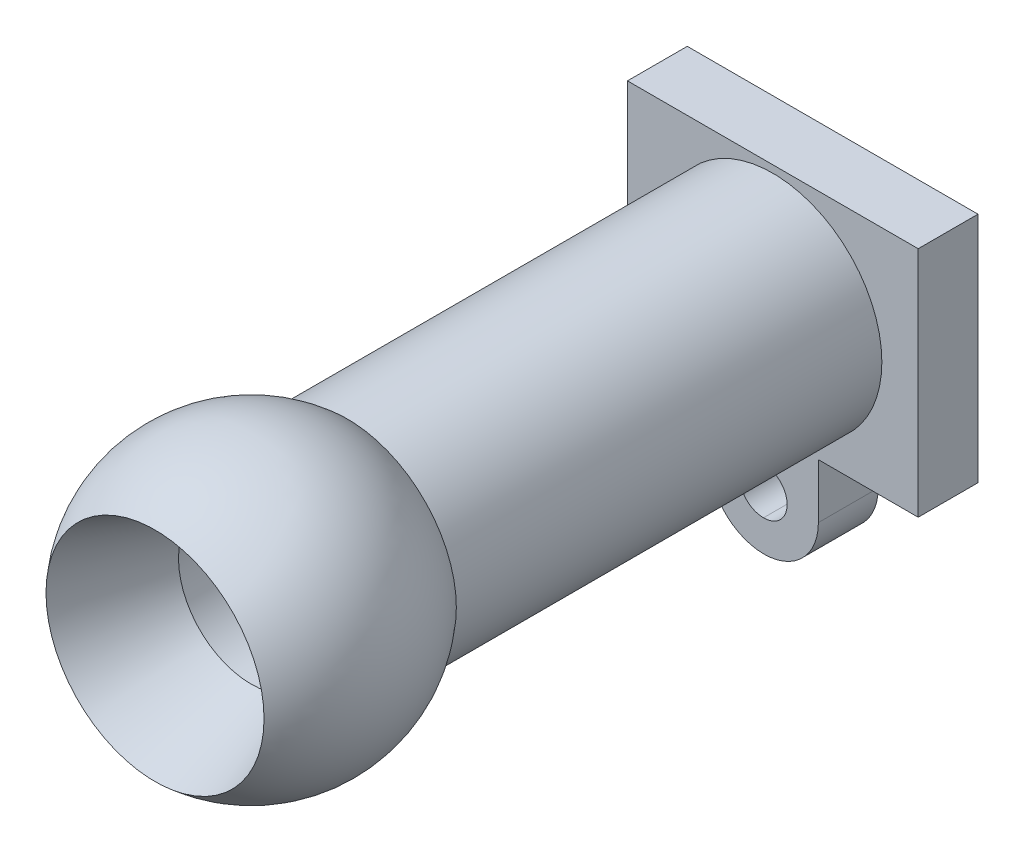
SolidWorks part; units mm, degrees
ref_plane "Front Plane" through (0, 0, 0) normal (0, 0, 1) x (1, 0, 0)
ref_plane "Top Plane" through (0, 0, 0) normal (0, 1, 0) x (1, 0, 0)
ref_plane "Right Plane" through (0, 0, 0) normal (1, 0, 0) x (0, 0, -1)
sketch "Sketch1" plane through (0, 0, 0) normal (0, 0, 1) x (1, 0, 0)
  line L0 (0, 10) -> (0, -10)
  arc A0 (0, -10) -> (0, 10) centre (0, 0) ccw
  dimension "D1" = 20
revolve "Revolve2" add sketch "Sketch1" angle 360 about L0
sketch "Sketch7" plane through (0, 0, 0) normal (0, 0, 1) x (1, 0, 0)
  circle A2 centre (0, 0) radius 7.5
  dimension "D1" = 15
extrude "Boss-Extrude1" add sketch "Sketch7" against normal blind 40
sketch "Sketch9" plane through (0, 0, -40) normal (0, 0, -1) x (-1, 0, 0)
  line L1 (-10, -8) -> (10, -8)
  line L2 (-10, -8) -> (-10, 8)
  line L3 (-10, 8) -> (10, 8)
  line L4 (10, -8) -> (10, 8)
  line L5 (-10, -8) -> (10, 8) construction
  line L6 (-10, 8) -> (10, -8) construction
  point P0 (0, 0)
  dimension "D1" = 20
  dimension "D2" = 16
extrude "Boss-Extrude2" add sketch "Sketch9" against normal up to surface (4.114 mm away)
sketch "Sketch10" plane through (0, 0, -40) normal (0, 0, -1) x (-1, 0, 0)
  line L0 (-10, -8) -> (10, -8) construction
  line L1 (4.3661, -8) -> (-3.1339, -8)
  line L2 (4.3661, -8) -> (4.3661, -15.5)
  line L3 (4.3661, -15.5) -> (-3.1339, -15.5)
  line L4 (-3.1339, -8) -> (-3.1339, -15.5)
  line L5 (4.3661, -8) -> (-3.1339, -15.5) construction
  line L6 (4.3661, -15.5) -> (-3.1339, -8) construction
  point P0 (0.6161, -11.75)
  dimension "D1" = 7.5
  dimension "D2" = 7.5
extrude "Boss-Extrude3" add sketch "Sketch10" against normal up to surface (4.114 mm away) up to face at (0, -7.5, -35.886)
sketch "Sketch11" plane through (0, 0, -40) normal (0, 0, 1) x (1, 0, 0)
  line L0 (-4.3661, -11.75) -> (-0.6621, -11.75) construction
  line L2 (-0.6161, -15.5) -> (-0.6621, -11.75) construction
  line L3 (3.1339, -15.5) -> (-4.3661, -15.5) construction
  line L4 (-4.3661, -15.5) -> (-4.3661, -8) construction
  circle A0 centre (-0.6621, -11.75) radius 1.6
  dimension "D1" = 3.2
extrude "Cut-Extrude2" cut sketch "Sketch11" along normal up to surface (4.114 mm away) contours A0 up to face at (0, -7.5, -35.886)
sketch "Sketch2" plane through (0, 0, 0) normal (0, 0, 1) x (1, 0, 0)
  circle A0 centre (0, 0) radius 5
  dimension "D1" = 10
extrude "Cut-Extrude1" cut sketch "Sketch2" against normal through all both and the other way through all
ref_axis "Axis2" through (0, 0, -40) along (0, 0, 1)
sketch "Sketch4" plane through (0, 0, 0) normal (0, 1, 0) x (1, 0, 0)
  line L0 (0, 0) -> (-5, 0)
  line L1 (0, 0) -> (0, -10)
  line L2 (0, -10) -> (-8.7787, -10)
  line L3 (-8.7787, -10) -> (-5, 0)
  line L4 (-5, 0) -> (-5, -10) construction
  dimension "D1" = 5
  dimension "D2" = 10
  dimension "D3" = 20.7
revolve "Cut-Revolve1" cut sketch "Sketch4" angle 360 about axis through (0, 0, -40) along (0, 0, 1)
sketch "Sketch14" plane through (0, 0, -40) normal (0, 0, -1) x (-1, 0, 0)
  line L0 (0.6161, -15.5) -> (0.6161, -11.75) construction
  line L1 (-3.1339, -15.5) -> (4.3661, -15.5) construction
  line L2 (4.3661, -11.75) -> (0.6161, -11.75) construction
  line L3 (4.3661, -15.5) -> (4.3661, -8) construction
  circle A0 centre (0.6161, -11.75) radius 1.6
  dimension "D1" = 3.2
extrude "Cut-Extrude4" cut sketch "Sketch14" against normal through all
fillet "Fillet4" radius 3.75 2 edges at (3.1339, -15.5, -37.943) (-4.3661, -15.5, -37.943)
